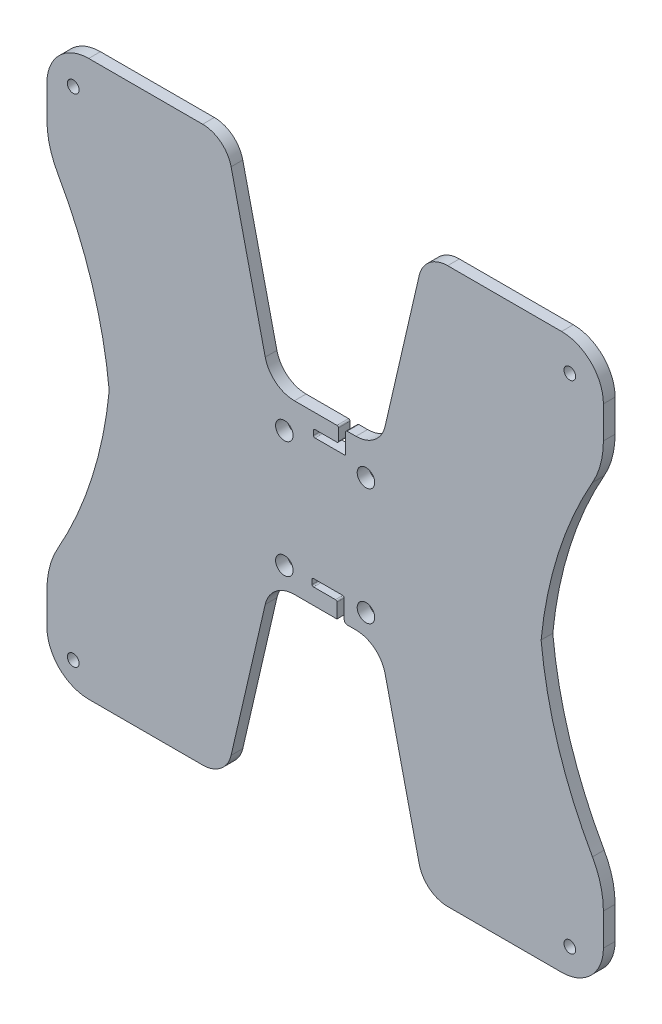
SolidWorks part; units mm, degrees
ref_plane "Front Plane" through (0, 0, 0) normal (0, 0, 1) x (1, 0, 0)
ref_plane "Top Plane" through (0, 0, 0) normal (0, 1, 0) x (1, 0, 0)
ref_plane "Right Plane" through (0, 0, 0) normal (1, 0, 0) x (0, 0, -1)
sketch "Sketch2" plane through (0, 0, 0) normal (0, 0, 1) x (1, 0, 0)
  line L3 (94.3754, -52.7044) -> (94.3754, -56.7044)
  line L4 (93.8754, -57.2044) -> (86.3754, -57.2044)
  line L5 (85.8754, -57.7044) -> (85.8754, -59.2044)
  line L6 (86.3754, -59.7044) -> (96.3754, -59.7044)
  line L7 (96.8754, -59.2044) -> (96.8754, -52.7044)
  line L8 (97.3754, -52.2044) -> (100.3754, -52.2044)
  line L9 (110.3627, -44.2602) -> (122.0425, 6.3307)
  line L10 (131.7862, 14.0812) -> (170.7845, 14.0812)
  line L11 (185.0955, -0.2297) -> (185.0955, -11.2297)
  line L16 (96.3754, -108.6331) -> (96.3754, -102.1331)
  line L17 (95.8754, -101.6331) -> (85.8754, -101.6331)
  line L18 (85.3754, -102.1331) -> (85.3754, -103.6331)
  line L19 (85.8754, -104.1331) -> (93.3754, -104.1331)
  line L20 (93.8754, -104.6331) -> (93.8754, -108.6331)
  line L26 (163.7717, -80.9188) -> (-81.9172, -80.9188) construction
  line L27 (97.3754, -109.6331) -> (100.3754, -109.6331)
  line L28 (185.0955, -161.6078) -> (185.0955, -150.6078)
  line L29 (131.7862, -175.9188) -> (170.7845, -175.9188)
  line L30 (110.3627, -117.5774) -> (122.0425, -168.1683)
  line L31 (185.0955, -161.6078) -> (-5.4045, -161.6078) construction
  line L32 (89.8455, -161.6078) -> (89.8455, -80.9188) construction
  line L33 (82.3155, -52.2044) -> (79.3155, -52.2044)
  line L34 (82.3155, -109.6331) -> (79.3155, -109.6331)
  line L35 (15.9192, -80.9188) -> (261.6081, -80.9188) construction
  line L36 (69.3282, -117.5774) -> (57.6484, -168.1683)
  line L37 (47.9047, -175.9188) -> (8.9064, -175.9188)
  line L38 (-5.4045, -161.6078) -> (-5.4045, -150.6078)
  line L39 (-5.4045, -0.2297) -> (-5.4045, -11.2297)
  line L40 (47.9047, 14.0812) -> (8.9064, 14.0812)
  line L41 (69.3282, -44.2602) -> (57.6484, 6.3307)
  line L42 (82.3155, -52.2044) -> (93.8754, -52.2044)
  line L43 (82.3155, -109.6331) -> (93.8754, -109.6331)
  line L44 (93.8754, -108.6331) -> (93.8754, -109.6331)
  line L45 (142.4554, -175.9188) -> (142.4554, 14.0812) construction
  arc A2 (94.3754, -52.7044) -> (93.8754, -52.2044) centre (93.8754, -52.7044) ccw
  arc A3 (93.8754, -57.2044) -> (94.3754, -56.7044) centre (93.8754, -56.7044) ccw
  arc A5 (85.8754, -59.2044) -> (86.3754, -59.7044) centre (86.3754, -59.2044) ccw
  arc A6 (86.3754, -57.2044) -> (85.8754, -57.7044) centre (86.3754, -57.7044) ccw
  arc A7 (96.3754, -59.7044) -> (96.8754, -59.2044) centre (96.3754, -59.2044) ccw
  arc A8 (97.3754, -52.2044) -> (96.8754, -52.7044) centre (97.3754, -52.7044) ccw
  arc A9 (100.3754, -52.2044) -> (110.3627, -44.2602) centre (100.3754, -41.9544) ccw
  arc A10 (131.7862, 14.0812) -> (122.0425, 6.3307) centre (131.7862, 4.0812) ccw
  arc A11 (185.0955, -0.2297) -> (170.7845, 14.0812) centre (170.7845, -0.2297) ccw
  arc A12 (181.353, -25.4269) -> (185.0955, -11.2297) centre (156.2955, -11.2297) ccw
  arc A13 (181.353, -25.4269) -> (163.7717, -80.9188) centre (303.5955, -94.6875) ccw
  arc A18 (96.3754, -108.6331) -> (97.3754, -109.6331) centre (97.3754, -108.6331) ccw
  arc A19 (96.3754, -102.1331) -> (95.8754, -101.6331) centre (95.8754, -102.1331) ccw
  arc A20 (85.8754, -101.6331) -> (85.3754, -102.1331) centre (85.8754, -102.1331) ccw
  arc A21 (85.3754, -103.6331) -> (85.8754, -104.1331) centre (85.8754, -103.6331) ccw
  arc A22 (93.8754, -104.6331) -> (93.3754, -104.1331) centre (93.3754, -104.6331) ccw
  arc A31 (79.3155, -109.6331) -> (69.3282, -117.5774) centre (79.3155, -119.8831) ccw
  arc A32 (181.353, -136.4106) -> (163.7717, -80.9188) centre (303.5955, -67.15) cw
  arc A33 (181.353, -136.4106) -> (185.0955, -150.6078) centre (156.2955, -150.6078) cw
  arc A34 (185.0955, -161.6078) -> (170.7845, -175.9188) centre (170.7845, -161.6078) cw
  arc A35 (131.7862, -175.9188) -> (122.0425, -168.1683) centre (131.7862, -165.9188) cw
  arc A36 (100.3754, -109.6331) -> (110.3627, -117.5774) centre (100.3754, -119.8831) cw
  arc A37 (47.9047, -175.9188) -> (57.6484, -168.1683) centre (47.9047, -165.9188) ccw
  arc A38 (-5.4045, -161.6078) -> (8.9064, -175.9188) centre (8.9064, -161.6078) ccw
  arc A39 (-1.6621, -136.4106) -> (-5.4045, -150.6078) centre (23.3955, -150.6078) ccw
  arc A40 (-1.6621, -136.4106) -> (15.9192, -80.9188) centre (-123.9045, -67.15) ccw
  arc A41 (-1.6621, -25.4269) -> (15.9192, -80.9188) centre (-123.9045, -94.6875) cw
  arc A42 (-1.6621, -25.4269) -> (-5.4045, -11.2297) centre (23.3955, -11.2297) cw
  arc A43 (-5.4045, -0.2297) -> (8.9064, 14.0812) centre (8.9064, -0.2297) cw
  arc A44 (47.9047, 14.0812) -> (57.6484, 6.3307) centre (47.9047, 4.0812) cw
  arc A45 (79.3155, -52.2044) -> (69.3282, -44.2602) centre (79.3155, -41.9544) cw
  dimension "D6" = 190.5
  dimension "D8" = 1
  dimension "D9" = 1
  dimension "D12" = 1
  dimension "D13" = 1
  dimension "D17" = 1
  dimension "D18" = 1
  dimension "D40" = 2
  dimension "D42" = 1
  dimension "D44" = 1
  dimension "D45" = 1
  dimension "D48" = 1
  dimension "D5" = 190
  dimension "D10" = 7.5
  dimension "D11" = 4
  dimension "D14" = 1.5
  dimension "D15" = 2.5
  dimension "D16" = 10
  dimension "D19" = 6.5
  dimension "D20" = 3
  dimension "D25" = 103
  dimension "D30" = 118.5
  dimension "D41" = 6.5
  dimension "D43" = 10
  dimension "D46" = 1.5
  dimension "D47" = 7.5
  dimension "D49" = 4
extrude "Boss-Extrude1" add sketch "Sketch2" along normal blind 4
sketch "Sketch3" plane through (0, 0, 4) normal (0, 0, 1) x (1, 0, 0)
  line L0 (170.7845, 14.0812) -> (131.7862, 14.0812) construction
  line L1 (-5.4045, -0.2297) -> (-5.4045, -11.2297) construction
  line L2 (8.9064, 14.0812) -> (170.7845, 14.0812) construction
  line L3 (89.8455, 14.0812) -> (89.8455, -175.9188) construction
  line L4 (75.8755, -62.7419) -> (103.8155, -62.7419) construction
  line L5 (8.9064, -175.9188) -> (170.7845, -175.9188) construction
  circle A0 centre (3.5955, 3.0812) radius 2
  circle A1 centre (3.5955, -166.9188) radius 2
  circle A2 centre (75.8755, -62.7419) radius 3
  circle A3 centre (103.8155, -62.7419) radius 3
  circle A4 centre (75.8755, -102.7419) radius 3
  circle A5 centre (103.8155, -102.7419) radius 3
  circle A6 centre (173.5955, -166.9188) radius 2
  circle A7 centre (173.5955, 3.0812) radius 2
  arc A8 (170.7845, -175.9188) -> (185.0955, -161.6078) centre (170.7845, -161.6078) ccw construction
  point P20 (89.8455, -62.7419)
  point P28 (0, 0)
  point P34 (0, 0)
  dimension "D1" = 170
  dimension "D3" = 170
  dimension "D4" = 11
  dimension "D5" = 27.94
  dimension "D6" = 40
  dimension "D7" = 9
  dimension "D8" = 6
  dimension "D9" = 6
  dimension "D10" = 6
  dimension "D11" = 6
extrude "Cut-Extrude1" cut sketch "Sketch3" against normal blind 4
ref_plane "Plane1" through (8.9064, 14.0812, 4) normal (-1, 0, 0) x (0, 0, 1)
sketch "Sketch5" plane through (0, 0, 4) normal (0, 0, 1) x (1, 0, 0)
  line L3 (44.9827, 10.7712) -> (44.9827, -167.2515) construction
